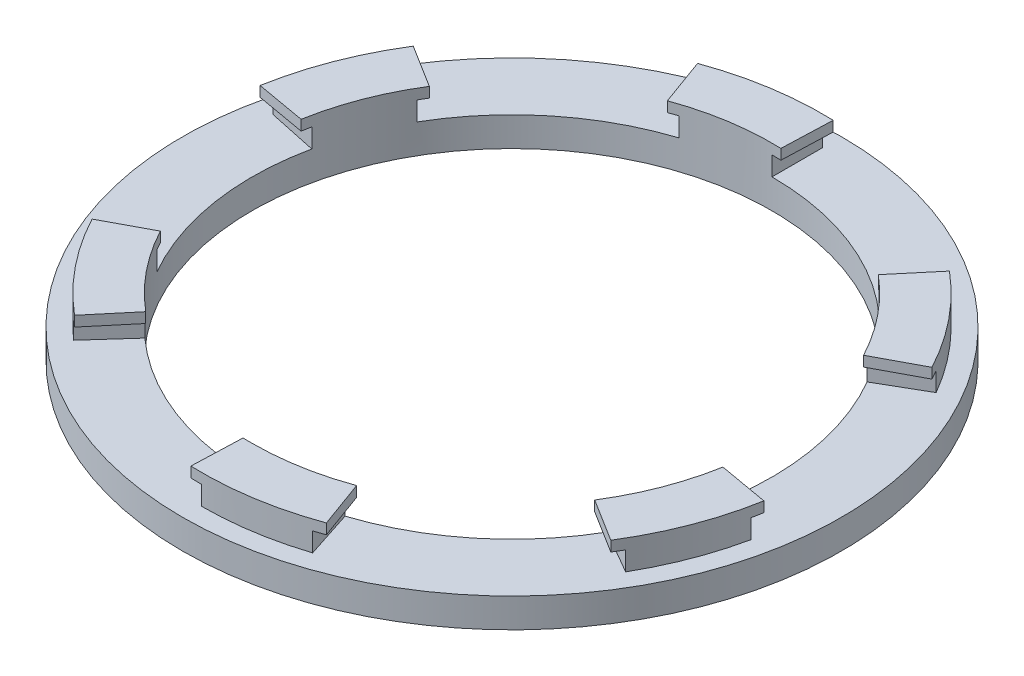
SolidWorks part; units mm, degrees
ref_plane "Front Plane" through (0, 0, 0) normal (0, 0, 1) x (1, 0, 0)
ref_plane "Top Plane" through (0, 0, 0) normal (0, 1, 0) x (1, 0, 0)
ref_plane "Right Plane" through (0, 0, 0) normal (1, 0, 0) x (0, 0, -1)
sketch "Sketch2" plane through (0, 0, 0) normal (0, 1, 0) x (1, 0, 0)
  circle A0 centre (0, 0) radius 17.75
  circle A1 centre (0, 0) radius 22.5
  dimension "D1" = 35.5
  dimension "D2" = 45
extrude "Boss-Extrude1" add sketch "Sketch2" along normal blind 2
sketch "Sketch3" plane through (0, 2, 0) normal (0, 1, 0) x (1, 0, 0)
  line L0 (0, 0) -> (0, 22.5) construction
  line L1 (-6.9529, 21.3988) -> (0, 0)
  line L2 (0, 0) -> (-6.9529, 21.3988) construction
  line L3 (0, 0) -> (0, 22.5)
  line L4 (0.7399, 21.1871) -> (0.6195, 17.7392)
  line L5 (-7.2508, 19.9215) -> (0.7399, 21.1871) construction
  line L6 (-6.9529, 21.3988) -> (0, 22.5) construction
  line L7 (-7.2508, 19.9215) -> (-6.0709, 16.6795)
  circle A0 centre (0, 0) radius 22.5 construction
  circle A1 centre (0, 0) radius 21.2
  circle A2 centre (0, 0) radius 17.75 construction
  arc A3 (-7.2508, 19.9215) -> (0.7399, 21.1871) centre (0, 0) cw
  arc A4 (-6.0709, 16.6795) -> (0.6195, 17.7392) centre (0, 0) cw
  point P13 (0.2413, 17.7484)
  point P17 (0, 0)
  point P18 (-7.2508, 19.9215)
  circle M5 centre (0, 0) radius 17.75
  dimension "D1" = 1.3
  dimension "D2" = 18
  dimension "D3" = 22
extrude "Boss-Extrude2" add sketch "Sketch3" along normal blind 2 contours L3 A1 L1 M5 region at (-3.042, 2, -19.2063)
extrude "Boss-Extrude3" add sketch "Sketch3<4>" along normal blind 0.7 from offset 1.3 contours L4 A1 L3 M5 | L1 A1 L7 M5 region at (-6.3567, 2, -18.4612) region at (0.3408, 2, -19.522)
sketch "Sketch3<4>" plane through (0, 2, 0) normal (0, 1, 0) x (1, 0, 0) same geometry as "Sketch3"
pattern_circular "CirPattern1" count 6 over 360 about axis through (0, 2, 0) along (0, -1, 0) of "Boss-Extrude2", "Boss-Extrude3" reverse direction yes
